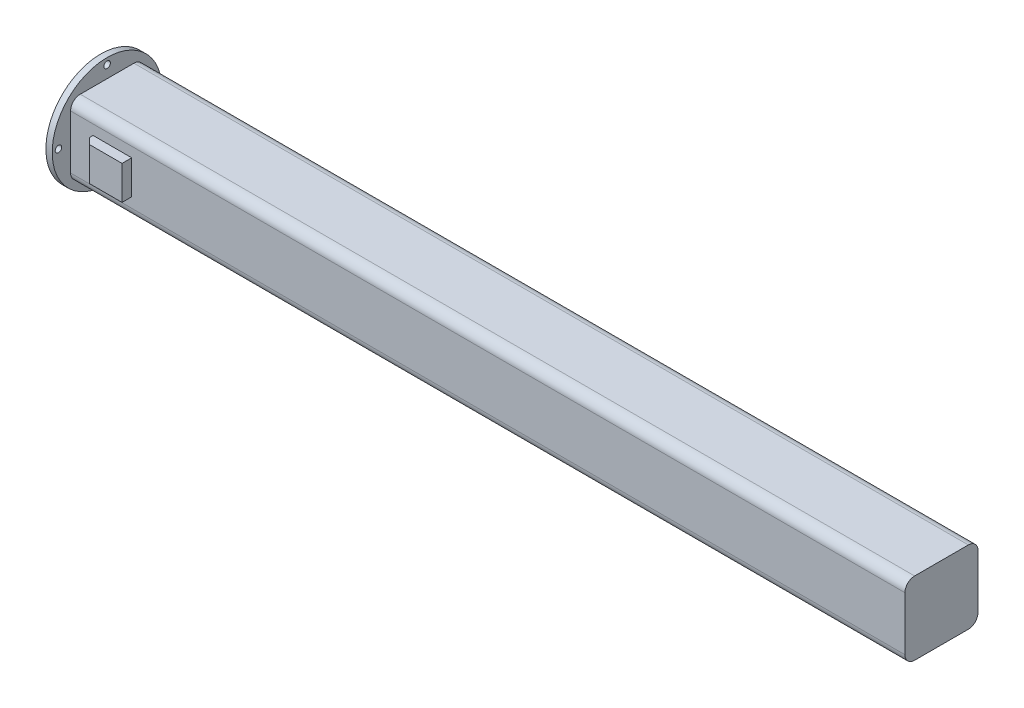
SolidWorks part; units mm, degrees
material "Plain Carbon Steel"
ref_plane "Front Plane" through (0, 0, 0) normal (0, 0, 1) x (1, 0, 0)
ref_plane "Top Plane" through (0, 0, 0) normal (0, 1, 0) x (1, 0, 0)
ref_plane "Right Plane" through (0, 0, 0) normal (1, 0, 0) x (0, 0, -1)
sketch "Sketch3" plane through (0, 0, 0) normal (1, 0, 0) x (0, 0, -1)
  line L1 (-75.5, -75.5) -> (75.5, -75.5)
  line L2 (-75.5, -75.5) -> (-75.5, 75.5)
  line L3 (-75.5, 75.5) -> (75.5, 75.5)
  line L4 (75.5, -75.5) -> (75.5, 75.5)
  line L5 (-75.5, -75.5) -> (75.5, 75.5) construction
  line L6 (-75.5, 75.5) -> (75.5, -75.5) construction
  point P0 (0, 0)
  dimension "D1" = 151
extrude "Boss-Extrude2" add sketch "Sketch3" along normal blind 1724.45
sketch "Sketch4" plane through (0, 0, 0) normal (-1, 0, 0) x (0, 0, 1)
  line L0 (75.5, 75.5) -> (75.5, -75.5) construction
  circle A0 centre (0, 0) radius 113.5
  point P3 (113.5, 0)
  dimension "D1" = 38
extrude "Boss-Extrude3" add sketch "Sketch4" along normal blind 13
sketch "Sketch5" plane through (0, 0, 0) normal (1, 0, 0) x (0, 0, -1)
  circle A0 centre (100.5, 0) radius 6.7462
  circle A1 centre (0, 0) radius 113.5 construction
  point P2 (113.5, 0)
  dimension "D1" = 13
  dimension "D2" = 13.4925
extrude "Cut-Extrude1" cut sketch "Sketch5" against normal up to surface (13 mm away) contours A0 up to face at (-13, 0, 113.5)
pattern_circular "CirPattern1" count 4 over 360 about axis through (0, 0, 0) along (-1, 0, 0) of "Cut-Extrude1"
fillet "Fillet1" radius 20 4 edges at (862.225, 75.5, 75.5) (862.225, 75.5, -75.5) (862.225, -75.5, 75.5) (862.225, -75.5, -75.5)
sketch "Sketch6" plane through (0, 0, -75.5) normal (0, 0, -1) x (-1, 0, 0)
  line L0 (0, -55.5) -> (0, 55.5) construction
  line L1 (-46.4, -34.925) -> (-126.4, -34.925)
  line L2 (-46.4, -34.925) -> (-46.4, 34.925)
  line L3 (-46.4, 34.925) -> (-126.4, 34.925)
  line L4 (-126.4, -34.925) -> (-126.4, 34.925)
  point P6 (0, 0)
  dimension "D1" = 46.4
  dimension "D2" = 80
  dimension "D3" = 69.85
  dimension "D4" = 34.925
extrude "Boss-Extrude4" add sketch "Sketch6" along normal blind 20
chamfer "Chamfer1" distance 13 angle 45 1 edges at (46.4, 0, -95.5)
fillet "Fillet2" radius 2 2 edges at (92.9, 34.925, -95.5) (92.9, -34.925, -95.5)
mirror "Mirror1" about plane through (0, 0, 0) normal (0, 0, 1) of "Chamfer1", "Boss-Extrude4"
ref_plane "Plane1" through (0, 0, 0) normal (0, 0, -1) x (-1, 0, 0)
shell "Shell1" thickness 5 removed face at (-13, 0, 107.2462)
